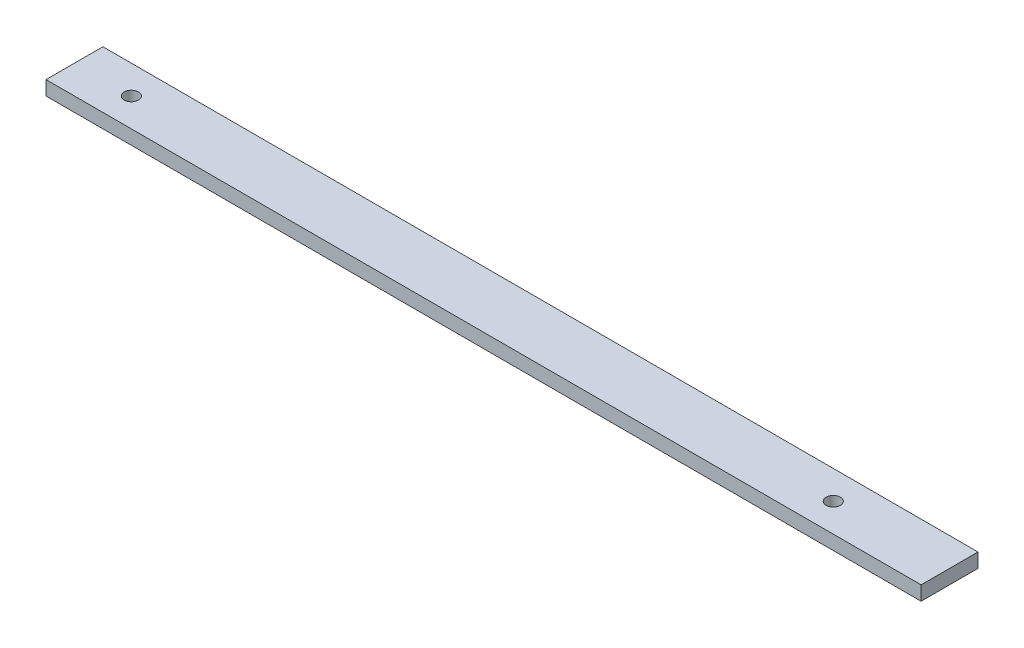
SolidWorks part; units mm, degrees
material "6061 Alloy"
ref_plane "Front Plane" through (0, 0, 0) normal (0, 0, 1) x (1, 0, 0)
ref_plane "Top Plane" through (0, 0, 0) normal (0, 1, 0) x (1, 0, 0)
ref_plane "Right Plane" through (0, 0, 0) normal (1, 0, 0) x (0, 0, -1)
sketch "Sketch1" plane through (0, 0, 0) normal (0, 1, 0) x (1, 0, 0)
  line L1 (0, 0) -> (390.652, 0)
  line L2 (0, 0) -> (0, -25.4)
  line L3 (0, -25.4) -> (390.652, -25.4)
  line L4 (390.652, 0) -> (390.652, -25.4)
  dimension "D1" = 390.652
  dimension "D2" = 25.4
extrude "Boss-Extrude1" add sketch "Sketch1" along normal blind 6.35
sketch "Sketch2" plane through (0, 0, 0) normal (0, -1, 0) x (1, 0, 0)
  line L0 (0, 0) -> (0, 25.4) construction
  line L1 (390.652, 0) -> (0, 0) construction
  circle A0 centre (25.4, 12.7) radius 3.175
  circle A1 centre (338.739, 12.7) radius 3.175
  dimension "D1" = 6.35
  dimension "D2" = 25.4
  dimension "D4" = 313.339
  dimension "D5" = 6.35
  dimension "D6" = 12.7
  dimension "D3" = 12.7
extrude "Cut-Extrude1" cut sketch "Sketch2" against normal up to next
